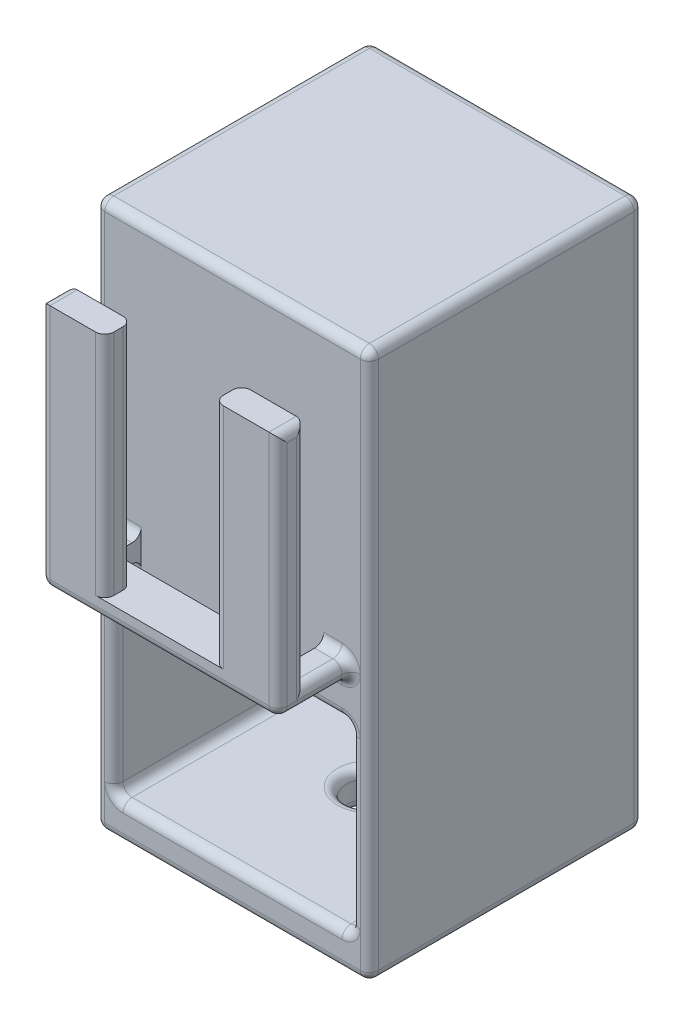
SolidWorks part; units mm, degrees
ref_plane "Front" through (0, 0, 0) normal (0, 0, 1) x (1, 0, 0)
ref_plane "Top" through (0, 0, 0) normal (0, 1, 0) x (1, 0, 0)
ref_plane "Right" through (0, 0, 0) normal (1, 0, 0) x (0, 0, -1)
sketch "Sketch3" plane through (0, 0, 0) normal (0, 0, 1) x (1, 0, 0)
  line L0 (0, 16.9545) -> (7, 16.9545) construction
  line L1 (0, 0) -> (26, 0)
  line L2 (0, 0) -> (0, 25)
  line L3 (0, 25) -> (26, 25)
  line L4 (26, 0) -> (26, 25)
  line L5 (0, 0) -> (7, 0)
  line L6 (0, 0) -> (0, 25)
  line L7 (0, 25) -> (7, 25)
  line L8 (7, 0) -> (7, 25)
  line L9 (26, 0) -> (19, 0)
  line L10 (26, 0) -> (26, 25)
  line L11 (26, 25) -> (19, 25)
  line L12 (19, 0) -> (19, 25)
  line L14 (19, 16.9545) -> (26, 16.9545) construction
  dimension "D1" = 26
  dimension "D2" = 25
  dimension "D3" = 12
extrude "Boss-Extrude2" add sketch "Sketch3" along normal blind 3 contours L1 L8 L3 L2 | L12 L1 L4 L3
sketch "Sketch4" plane through (26, 0, 0) normal (1, 0, 0) x (0, 0, -1)
  line L1 (-3, 0) -> (2, 0)
  line L2 (-3, 0) -> (-3, -2)
  line L3 (-3, -2) -> (2, -2)
  line L4 (2, 0) -> (2, -2)
  dimension "D1" = 2
  dimension "D2" = 2
extrude "Boss-Extrude3" add sketch "Sketch4" against normal blind 26
sketch "Sketch5" plane through (0, 0, -2) normal (0, 0, -1) x (-1, 0, 0)
  line L0 (0, 0) -> (-26, 0) construction
  line L1 (-26, -2) -> (-23, -2)
  line L2 (-26, -2) -> (-26, 0)
  line L3 (-26, 0) -> (-23, 0)
  line L4 (-23, -2) -> (-23, 0)
  line L5 (-13, 0) -> (-13, -2) construction
  line L6 (0, -2) -> (-26, -2) construction
  line L7 (0, 0) -> (-3, 0)
  line L8 (-3, -2) -> (-3, 0)
  line L9 (0, -2) -> (-3, -2)
  line L10 (0, -2) -> (0, 0)
  dimension "D1" = 3
extrude "Boss-Extrude4" add sketch "Sketch5" along normal blind 3
sketch "Sketch6" plane through (0, 0, -5) normal (0, 0, -1) x (-1, 0, 0)
  line L0 (-3, 0) -> (-23, 0) construction
  line L1 (-28, -30.0801) -> (2, -30.0801)
  line L2 (-28, -30.0801) -> (-28, 29.9199)
  line L3 (-28, 29.9199) -> (2, 29.9199)
  line L4 (2, -30.0801) -> (2, 29.9199)
  point P4 (-13, 29.9199)
  point P7 (-13, 0)
  dimension "D1" = 60
  dimension "D2" = 30
extrude "Boss-Extrude5" add sketch "Sketch6" along normal blind 30 contours L1 L4 L3 L2
sketch "Sketch7" plane through (0, 0, -5) normal (0, 0, 1) x (1, 0, 0)
  line L1 (0, -6.1568) -> (26, -6.1568)
  line L2 (0, -6.1568) -> (0, -26.1568)
  line L3 (0, -26.1568) -> (26, -26.1568)
  line L4 (26, -6.1568) -> (26, -26.1568)
  dimension "D1" = 20
extrude "Cut-Extrude2" cut sketch "Sketch7" against normal blind 43
sketch "Sketch8" plane through (0, -30.0801, 0) normal (0, -1, 0) x (1, 0, 0)
  line L0 (28, -35) -> (28, -5) construction
  line L1 (28, -35) -> (-2, -35) construction
  circle A0 centre (13, -20) radius 2.5
  point P4 (28, -20)
  point P7 (13, -35)
  dimension "D1" = 5
extrude "Cut-Extrude3" cut sketch "Sketch8" against normal blind 18 contours A0
fillet "Fillet2" radius 1 19 edges at (26, 11.5, 3) (19, 12.5, 0) (7, 12.5, 3) (0, 11.5, 3) (26, -2, -1) (0, -2, -1) (24.5, -2, -5) (13, -2, 3) (1.5, -2, -5) (1.5, 0, -5) (24.5, 0, -5) (0, 25, 1.5) (0, 0, -2.5) (0, 12.5, 0) (26, 25, 1.5) (26, 12.5, 0) (26, 0, -2.5) (7, 12.5, 0) (19, 12.5, 3)
sketch "Sketch9" plane through (0, 0, -35) normal (0, 0, -1) x (-1, 0, 0)
  line L1 (-26, -7.8902) -> (0, -7.8902)
  line L2 (-26, -7.8902) -> (-26, 24.7374)
  line L3 (-26, 24.7374) -> (0, 24.7374)
  line L4 (0, -7.8902) -> (0, 24.7374)
  line L5 (-26, -26.1568) -> (-26, -6.1568) construction
  line L8 (0, -6.1568) -> (0, -26.1568) construction
extrude "Cut-Extrude4" cut sketch "Sketch9" against normal blind 22
fillet "Fillet3" radius 1 30 edges at (13, -6.1568, -5) (26, -16.1568, -5) (0, -16.1568, -5) (0, -6.1568, -9) (26, -6.1568, -9) (13, -30.0801, -5) (13, -30.0801, -22.5) (-2, -30.0801, -20) (-2, -0.0801, -5) (-2, 29.9199, -20) (13, 29.9199, -5) (28, 29.9199, -20) (28, -30.0801, -20) (28, -0.0801, -5) (26, -26.1568, -20) (13, -26.1568, -5) (0, -26.1568, -20) (13, -26.1568, -22.5) (13, 29.9199, -35) (-2, -0.0801, -35) (13, -30.0801, -35) (28, -0.0801, -35) (13, -26.1568, -35) (0, -0.7097, -35) (13, 24.7374, -35) (26, -0.7097, -35) (13, -6.1568, -13) (26, 9.2903, -13) (13, 24.7374, -13) (0, 9.2903, -13)
